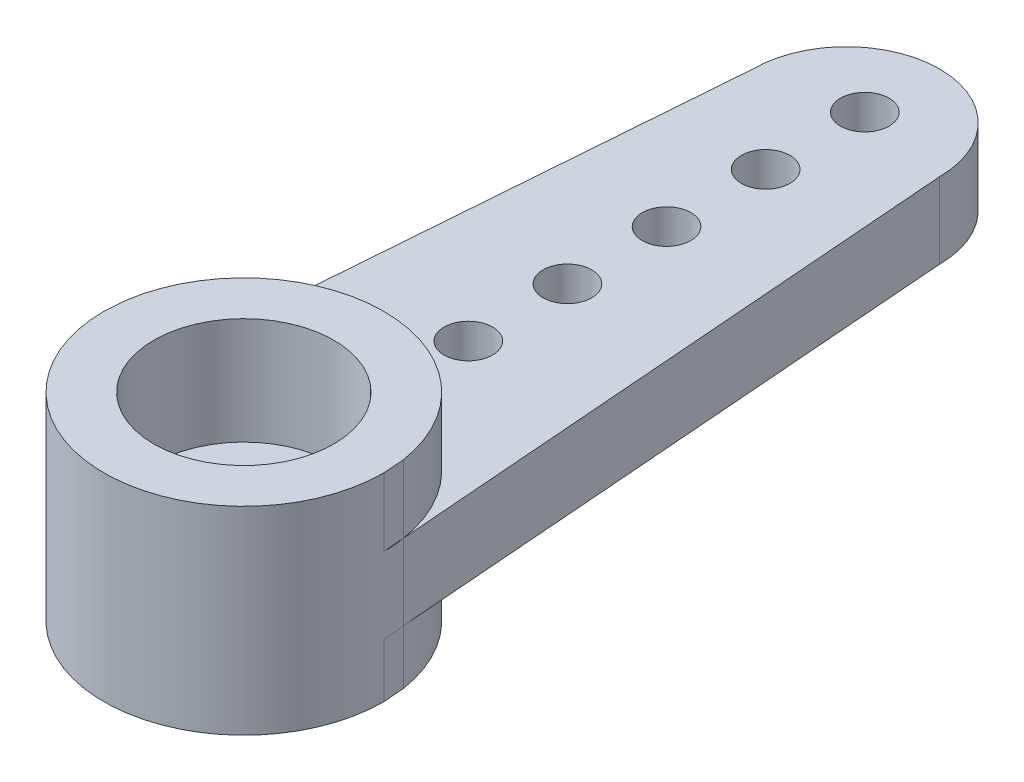
SolidWorks part; units mm, degrees
ref_plane "Front Plane" through (0, 0, 0) normal (0, 0, 1) x (1, 0, 0)
ref_plane "Top Plane" through (0, 0, 0) normal (0, 1, 0) x (1, 0, 0)
ref_plane "Right Plane" through (0, 0, 0) normal (1, 0, 0) x (0, 0, -1)
sketch "Sketch1" plane through (0, 0, 0) normal (0, 1, 0) x (1, 0, 0)
  line L0 (0, -3.6) -> (0, 17.9)
  line L1 (-2.4, 15.5) -> (-3.6, 0)
  line L2 (2.4, 15.5) -> (3.6, 0)
  circle A0 centre (0, 0) radius 3.6
  circle A1 centre (0, 15.5) radius 2.4
  circle A2 centre (0, 15.975) radius 0.625
  circle A4 centre (0, 13.425) radius 0.625
  circle A5 centre (0, 10.875) radius 0.625
  circle A6 centre (0, 8.325) radius 0.625
  circle A7 centre (0, 5.775) radius 0.625
  circle A8 centre (0, 0) radius 2.315
  circle A9 centre (0, 0) radius 1.265
  dimension "D1" = 7.2
  dimension "D3" = 4.8
  dimension "D5" = 1.25
  dimension "D12" = 4.63
  dimension "D13" = 2.53
  dimension "D2" = 21.5
  dimension "D4" = 2.4
  dimension "D6" = 1.925
  dimension "D7" = 2.55
  dimension "D8" = 2.55
  dimension "D9" = 2.55
  dimension "D10" = 2.55
  dimension "D11" = 5.775
extrude "Boss-Extrude2" add sketch "Sketch1" along normal blind 1.95 contours A7 L0 A0 L2 A1 A4 A5 A6 | A7 L0 A6 A5 A4 A1 L1 A0 | A4 L0 A2 A1 | A4 A1 L0 A2 | A0 | A9 region at (-1.6764, 0, -7.9884) region at (1.6764, 0, -7.9884) region at (-1.1225, 0, -15.5841) region at (1.1225, 0, -15.5841)
extrude "Boss-Extrude3" add sketch "Sketch1<4>" against normal blind 1.4 contours A8 L0 A0 L2 | A8 L0 A0 L1 region at (-2.4887, 0, 2.4887) region at (0.0805, 0, 2.9575)
sketch "Sketch1<4>" plane through (0, 0, 0) normal (0, 1, 0) x (1, 0, 0) same geometry as "Sketch1"
extrude "Boss-Extrude4" add sketch "Sketch1<5>" along normal blind 3.7 contours A8 L0 A0 L2 | A8 L0 A0 L1 region at (-2.4887, 0, 2.4887) region at (0.0805, 0, 2.9575)
sketch "Sketch1<5>" plane through (0, 0, 0) normal (0, 1, 0) x (1, 0, 0) same geometry as "Sketch1"
sketch "Sketch4" plane through (0, 1.95, 0) normal (0, 1, 0) x (1, 0, 0)
  circle A0 centre (0, 0) radius 1.265
  circle A1 centre (0, 0) radius 2.315
extrude "Cut-Extrude1" cut sketch "Sketch4" against normal blind 1
equation "\"D7@Sketch1\"=\"D6@Sketch1\"+0.625"
equation "\"D8@Sketch1\"=\"D7@Sketch1\""
equation "\"D9@Sketch1\"=\"D8@Sketch1\""
equation "\"D10@Sketch1\"=\"D7@Sketch1\""
